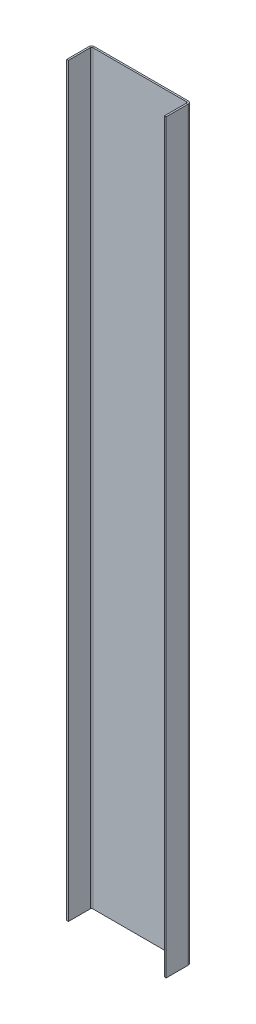
SolidWorks part; units mm, degrees
note: The reader was unsure of these and kept them because the rebuilt part matched: thickness of "Base-Flange1", "Edge-Flange1", "Sheet-Metal1", "Sheet-Metal2"; flange length of "Edge-Flange1".
ref_plane "Front Plane" through (0, 0, 0) normal (0, 0, 1) x (1, 0, 0)
ref_plane "Top Plane" through (0, 0, 0) normal (0, 1, 0) x (1, 0, 0)
ref_plane "Right Plane" through (0, 0, 0) normal (1, 0, 0) x (0, 0, -1)
sketch "Sketch1" plane through (0, 0, 0) normal (0, 0, 1) x (1, 0, 0)
  line L1 (-30, 225) -> (30, 225)
  line L2 (-30, 225) -> (-30, -225)
  line L3 (-30, -225) -> (30, -225)
  line L4 (30, 225) -> (30, -225)
  line L5 (-30, 225) -> (30, -225) construction
  line L6 (-30, -225) -> (30, 225) construction
  point P0 (0, 0)
  dimension "D1" = 450
  dimension "D2" = 60
base flange "Base-Flange1" sketch "Sketch1" thickness 1 reverse thickness direction no parameters "D1"=0.7366
edge flange "Edge-Flange1" sketch "Sketch10" flange profiles "Sketch10", "Sketch11" flange angle 90 flange length 15 flange position material inside bend radius 0.7366 thickness 1 relief rectangular parameters "D6"=10, "D8"=1
sketch "Sketch10" plane through (30, 0, 0) normal (1, 0, 0) x (0, 1, 0)
  line L2 (-225, 0) -> (-225, 14)
  line L3 (-225, 14) -> (225, 14)
  line L4 (225, 14) -> (225, 0)
  line L7 (-225, 0) -> (225, 0) construction
  line L8 (-225, 0) -> (225, 0)
sketch "Sketch11" plane through (-30, 0, 0) normal (-1, 0, 0) x (0, -1, 0)
  line L2 (-225, 0) -> (-225, 14)
  line L3 (-225, 14) -> (225, 14)
  line L4 (225, 14) -> (225, 0)
  line L7 (-225, 0) -> (225, 0) construction
  line L8 (-225, 0) -> (225, 0)
bend "EdgeBend1" bend radius 0.7366 bend angle 90 parameters "D5"=1
bend "EdgeBend2" bend radius 0.7366 bend angle 90 parameters "D5"=2
sketch "Bend-Lines1" [suppressed] plane through (0, 0, 0) normal (0, 1, 0) x (1, 0, 0)
sketch "Bounding-Box1" [suppressed] plane through (0, 0, 0) normal (0, 1, 0) x (1, 0, 0)
sheet metal parameters "Sheet-Metal1" thickness 1 parameters "D1"=0.7366
flat pattern "Flat-Pattern1" [suppressed]
sketch "Bend-Lines2" plane through (0, 0, 0) normal (0, 1, 0) x (1, 0, 0)
sketch3d "Bounding-Box2" [suppressed]
  line L0 (-15, 285, 0) -> (-15, -285, 0) construction
  line L1 (15, 285, 0) -> (15, -285, 0) construction
  line L2 (-15, 285, 0) -> (15, 285, 0) construction
  line L3 (-15, -285, 0) -> (15, -285, 0) construction
sheet metal parameters "Sheet-Metal2" thickness 1 parameters "D1"=0.7366, "D7"=2
flat pattern "Flat-Pattern1"
sketch "Bend-Lines2" plane through (0, 0, 0) normal (0, 0, 1) x (1, 0, 0)
  line L0 (-29.2346, 225) -> (-29.2346, -225) construction
  line L1 (29.2346, -225) -> (29.2346, 225) construction
  line L2 (-29.2346, 225) -> (-29.2346, -225) construction
  line L3 (29.2346, -225) -> (29.2346, 225) construction
sketch3d "Bounding-Box2" [suppressed]
  line L0 (43.4692, 225, 0) -> (43.4692, -225, 0) construction
  line L1 (-43.4692, 225, 0) -> (-43.4692, -225, 0) construction
  line L2 (43.4692, 225, 0) -> (-43.4692, 225, 0) construction
  line L3 (43.4692, -225, 0) -> (-43.4692, -225, 0) construction
bend of the flat pattern "Flatten-<EdgeBend1>1"
bend of the flat pattern "Flatten-<EdgeBend2>1"
